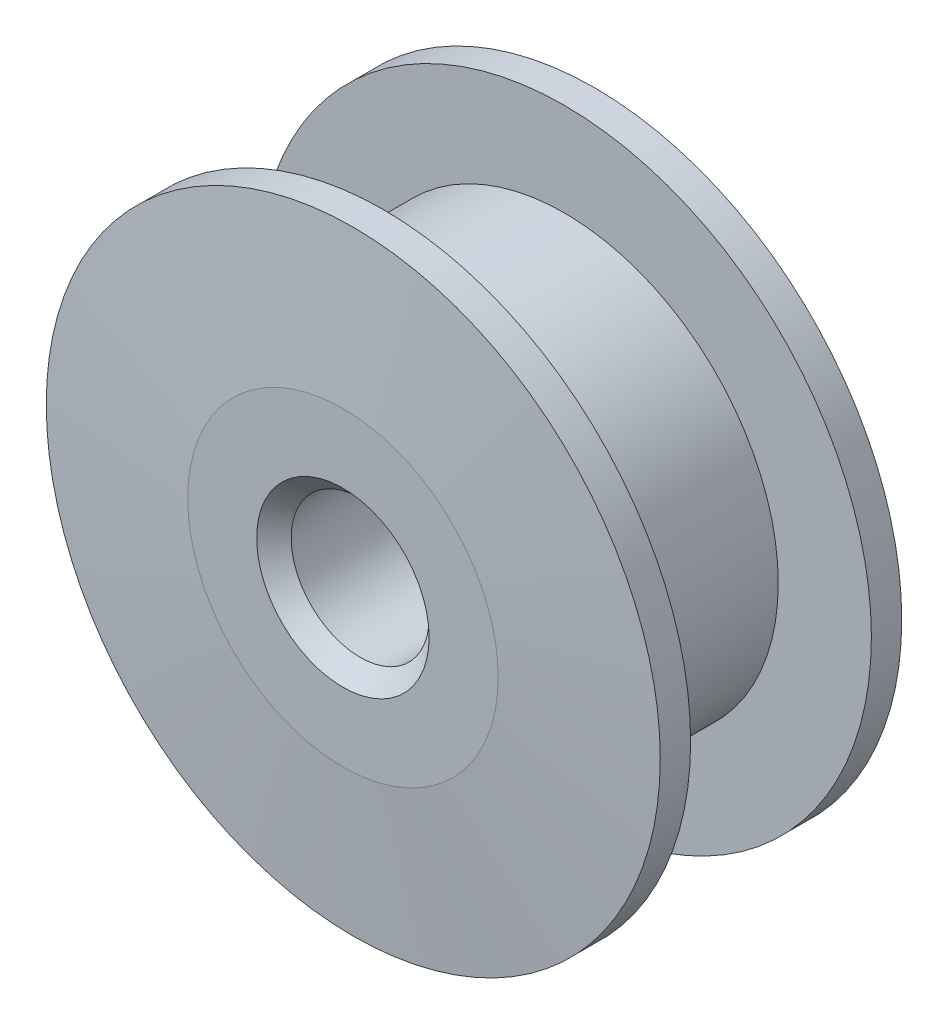
SolidWorks part; units mm, degrees
material "7075-T6，板材(SS)"
ref_plane "前视基准面" through (0, 0, 0) normal (0, 0, 1) x (1, 0, 0)
ref_plane "上视基准面" through (0, 0, 0) normal (0, 1, 0) x (1, 0, 0)
ref_plane "右视基准面" through (0, 0, 0) normal (1, 0, 0) x (0, 0, -1)
sketch "草图1" plane through (0, 0, 0) normal (0, 0, 1) x (1, 0, 0)
  circle A0 centre (0, 0) radius 4.45
  dimension "D1" = 8.9
extrude "拉伸1" add sketch "草图1" along normal mid plane 3.8
sketch "草图2" plane through (0, 0, 0) normal (0, 0, 1) x (1, 0, 0)
  circle A0 centre (0, 0) radius 4.45 construction
  circle A1 centre (0, 0) radius 4.45
  circle A2 centre (0, 0) radius 3.1
  dimension "D1" = 6.2
extrude "拉伸2" cut sketch "草图2" against normal mid plane 2.62
sketch "草图3" plane through (0, 0, 1.9) normal (0, 0, 1) x (1, 0, 0)
  circle A0 centre (0, 0) radius 1
  dimension "D1" = 2
extrude "拉伸3" cut sketch "草图3" against normal up to surface (3.8 mm away) up to face at (4.45, 0, -1.9)
chamfer "倒角1" distance 0.25 angle 45 2 edges at (1, 0, -1.9) (1, 0, 1.9)
chamfer "倒角2" distance 2 distance2 0.15 1 edges at (4.45, 0, -1.9) first distance on face at (1.25, 0, -1.9)
chamfer "倒角3" distance 0.15 distance2 2.2 1 edges at (4.45, 0, 1.9) first distance on face at (4.45, 0, 1.31)
